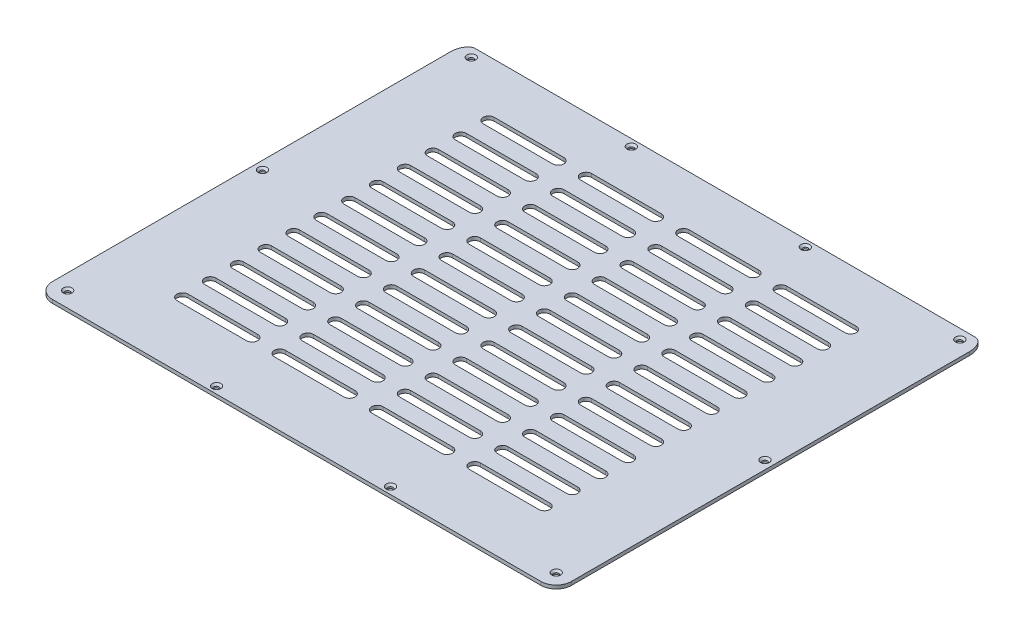
SolidWorks part; units mm, degrees
ref_plane "前基準面" through (0, 0, 0) normal (0, 0, 1) x (1, 0, 0)
ref_plane "上基準面" through (0, 0, 0) normal (0, 1, 0) x (1, 0, 0)
ref_plane "右基準面" through (0, 0, 0) normal (1, 0, 0) x (0, 0, -1)
sketch "草圖1" plane through (0, 0, 0) normal (0, 1, 0) x (1, 0, 0)
  line L1 (-186.5, -154) -> (186.5, -154)
  line L2 (-186.5, -154) -> (-186.5, 154)
  line L3 (-186.5, 154) -> (186.5, 154)
  line L4 (186.5, -154) -> (186.5, 154)
  line L5 (-186.5, -154) -> (186.5, 154) construction
  line L6 (-186.5, 154) -> (186.5, -154) construction
  point P0 (0, 0)
  dimension "D1" = 373
  dimension "D2" = 308
extrude "填料-伸長1" add sketch "草圖1" along normal blind 2.5
fillet "圓角1" radius 11 2 edges at (-186.5, 1.25, 154) (186.5, 1.25, 154)
fillet "圓角2" radius 7 1 edges at (-186.5, 1.25, -154) second distance 11 first distance on face at (0, 1.25, -154)
fillet "圓角3" radius 11 1 edges at (186.5, 1.25, -154) second distance 7 first distance on face at (186.5, 1.25, -5.5)
hole_wizard "M3 錐坑平頭螺釘的錐孔1" positions "草圖2" profile "草圖3" countersink size "M3" standard "ISO" end condition through all
sketch "草圖2" plane through (0, 2.5, 0) normal (0, 1, 0) x (1, 0, 0)
  line L0 (-175.5, -154) -> (175.5, -154) construction
  line L1 (-186.5, 143) -> (-186.5, -143) construction
  line L3 (179.5, 154) -> (-179.5, 154) construction
  line L4 (186.5, -143) -> (186.5, 143) construction
  point P0 (-175.5, 147)
  point P2 (-62.5, 149)
  point P4 (62.5, 149)
  point P6 (175.5, 147)
  point P8 (180.5, 2)
  point P10 (175.5, -143)
  point P12 (62.5, -149)
  point P14 (-62.5, -149)
  point P16 (-175.5, -143)
  point P18 (-180.5, 2)
  dimension "D1" = 11
  dimension "D2" = 11
  dimension "D3" = 113
  dimension "D4" = 125
  dimension "D5" = 113
  dimension "D6" = 11
  dimension "D7" = 5
  dimension "D8" = 5
  dimension "D9" = 5
  dimension "D10" = 5
  dimension "D11" = 7
  dimension "D12" = 7
  dimension "D13" = 11
  dimension "D14" = 6
  dimension "D15" = 6
  dimension "D16" = 11
  dimension "D17" = 145
  dimension "D18" = 145
  dimension "D19" = 113
  dimension "D20" = 125
sketch "草圖3" plane through (-175.5, 2.5, -147) normal (1, 0, 0) x (0, 0, 1)
  line L0 (0, 0) -> (0, 2.555)
  line L1 (0, 2.555) -> (1.8, 2.555)
  line L2 (1.8, 2.555) -> (1.8, 1.35)
  line L3 (1.8, 1.35) -> (3.15, 0)
  line L5 (3.15, 0) -> (0, 0)
  line L6 (-1.8, 1.35) -> (-3.15, 0) construction
  line L11 (0, -6.35) -> (0, 107.95) construction
  dimension "貫穿孔直徑" = 3.6
  dimension "貫穿孔深度" = 2.555
  dimension "近端錐孔直徑" = 6.3
  dimension "近端錐孔角度" = 90
sketch "草圖4" plane through (0, 2.5, 0) normal (0, 1, 0) x (1, 0, 0)
  line L0 (-130, 114) -> (-80, 114) construction
  line L1 (-130, 118) -> (-80, 118)
  line L2 (-130, 110) -> (-80, 110)
  line L3 (-186.5, 143) -> (-186.5, -143) construction
  line L4 (179.5, 154) -> (-179.5, 154) construction
  line L5 (-60, 114) -> (-10, 114) construction
  line L6 (-60, 118) -> (-10, 118)
  line L7 (-60, 110) -> (-10, 110)
  line L8 (10, 114) -> (60, 114) construction
  line L9 (10, 118) -> (60, 118)
  line L10 (10, 110) -> (60, 110)
  line L11 (80, 114) -> (130, 114) construction
  line L12 (80, 118) -> (130, 118)
  line L13 (80, 110) -> (130, 110)
  line L14 (-60, 94) -> (-10, 94) construction
  line L15 (-60, 98) -> (-10, 98)
  line L16 (-60, 90) -> (-10, 90)
  line L17 (10, 94) -> (60, 94) construction
  line L18 (10, 98) -> (60, 98)
  line L19 (10, 90) -> (60, 90)
  line L20 (80, 94) -> (130, 94) construction
  line L21 (80, 98) -> (130, 98)
  line L22 (80, 90) -> (130, 90)
  line L23 (-60, 74) -> (-10, 74) construction
  line L24 (-60, 78) -> (-10, 78)
  line L25 (-60, 70) -> (-10, 70)
  line L26 (10, 74) -> (60, 74) construction
  line L27 (10, 78) -> (60, 78)
  line L28 (10, 70) -> (60, 70)
  line L29 (80, 74) -> (130, 74) construction
  line L30 (80, 78) -> (130, 78)
  line L31 (80, 70) -> (130, 70)
  line L32 (-60, 54) -> (-10, 54) construction
  line L33 (-60, 58) -> (-10, 58)
  line L34 (-60, 50) -> (-10, 50)
  line L35 (10, 54) -> (60, 54) construction
  line L36 (10, 58) -> (60, 58)
  line L37 (10, 50) -> (60, 50)
  line L38 (80, 54) -> (130, 54) construction
  line L39 (80, 58) -> (130, 58)
  line L40 (80, 50) -> (130, 50)
  line L41 (-60, 34) -> (-10, 34) construction
  line L42 (-60, 38) -> (-10, 38)
  line L43 (-60, 30) -> (-10, 30)
  line L44 (10, 34) -> (60, 34) construction
  line L45 (10, 38) -> (60, 38)
  line L46 (10, 30) -> (60, 30)
  line L47 (80, 34) -> (130, 34) construction
  line L48 (80, 38) -> (130, 38)
  line L49 (80, 30) -> (130, 30)
  line L50 (-60, 14) -> (-10, 14) construction
  line L51 (-60, 18) -> (-10, 18)
  line L52 (-60, 10) -> (-10, 10)
  line L53 (10, 14) -> (60, 14) construction
  line L54 (10, 18) -> (60, 18)
  line L55 (10, 10) -> (60, 10)
  line L56 (80, 14) -> (130, 14) construction
  line L57 (80, 18) -> (130, 18)
  line L58 (80, 10) -> (130, 10)
  line L59 (-60, -6) -> (-10, -6) construction
  line L60 (-60, -2) -> (-10, -2)
  line L61 (-60, -10) -> (-10, -10)
  line L62 (10, -6) -> (60, -6) construction
  line L63 (10, -2) -> (60, -2)
  line L64 (10, -10) -> (60, -10)
  line L65 (80, -6) -> (130, -6) construction
  line L66 (80, -2) -> (130, -2)
  line L67 (80, -10) -> (130, -10)
  line L68 (-60, -26) -> (-10, -26) construction
  line L69 (-60, -22) -> (-10, -22)
  line L70 (-60, -30) -> (-10, -30)
  line L71 (10, -26) -> (60, -26) construction
  line L72 (10, -22) -> (60, -22)
  line L73 (10, -30) -> (60, -30)
  line L74 (80, -26) -> (130, -26) construction
  line L75 (80, -22) -> (130, -22)
  line L76 (80, -30) -> (130, -30)
  line L77 (-60, -46) -> (-10, -46) construction
  line L78 (-60, -42) -> (-10, -42)
  line L79 (-60, -50) -> (-10, -50)
  line L80 (10, -46) -> (60, -46) construction
  line L81 (10, -42) -> (60, -42)
  line L82 (10, -50) -> (60, -50)
  line L83 (80, -46) -> (130, -46) construction
  line L84 (80, -42) -> (130, -42)
  line L85 (80, -50) -> (130, -50)
  line L86 (-60, -66) -> (-10, -66) construction
  line L87 (-60, -62) -> (-10, -62)
  line L88 (-60, -70) -> (-10, -70)
  line L89 (10, -66) -> (60, -66) construction
  line L90 (10, -62) -> (60, -62)
  line L91 (10, -70) -> (60, -70)
  line L92 (80, -66) -> (130, -66) construction
  line L93 (80, -62) -> (130, -62)
  line L94 (80, -70) -> (130, -70)
  line L95 (-60, -86) -> (-10, -86) construction
  line L96 (-60, -82) -> (-10, -82)
  line L97 (-60, -90) -> (-10, -90)
  line L98 (10, -86) -> (60, -86) construction
  line L99 (10, -82) -> (60, -82)
  line L100 (10, -90) -> (60, -90)
  line L101 (80, -86) -> (130, -86) construction
  line L102 (80, -82) -> (130, -82)
  line L103 (80, -90) -> (130, -90)
  line L104 (-60, -106) -> (-10, -106) construction
  line L105 (-60, -102) -> (-10, -102)
  line L106 (-60, -110) -> (-10, -110)
  line L107 (10, -106) -> (60, -106) construction
  line L108 (10, -102) -> (60, -102)
  line L109 (10, -110) -> (60, -110)
  line L110 (80, -106) -> (130, -106) construction
  line L111 (80, -102) -> (130, -102)
  line L112 (80, -110) -> (130, -110)
  line L113 (-130, 94) -> (-80, 94) construction
  line L114 (-130, 98) -> (-80, 98)
  line L115 (-130, 90) -> (-80, 90)
  line L116 (-130, 74) -> (-80, 74) construction
  line L117 (-130, 78) -> (-80, 78)
  line L118 (-130, 70) -> (-80, 70)
  line L119 (-130, 54) -> (-80, 54) construction
  line L120 (-130, 58) -> (-80, 58)
  line L121 (-130, 50) -> (-80, 50)
  line L122 (-130, 34) -> (-80, 34) construction
  line L123 (-130, 38) -> (-80, 38)
  line L124 (-130, 30) -> (-80, 30)
  line L125 (-130, 14) -> (-80, 14) construction
  line L126 (-130, 18) -> (-80, 18)
  line L127 (-130, 10) -> (-80, 10)
  line L128 (-130, -6) -> (-80, -6) construction
  line L129 (-130, -2) -> (-80, -2)
  line L130 (-130, -10) -> (-80, -10)
  line L131 (-130, -26) -> (-80, -26) construction
  line L132 (-130, -22) -> (-80, -22)
  line L133 (-130, -30) -> (-80, -30)
  line L134 (-130, -46) -> (-80, -46) construction
  line L135 (-130, -42) -> (-80, -42)
  line L136 (-130, -50) -> (-80, -50)
  line L137 (-130, -66) -> (-80, -66) construction
  line L138 (-130, -62) -> (-80, -62)
  line L139 (-130, -70) -> (-80, -70)
  line L140 (-130, -86) -> (-80, -86) construction
  line L141 (-130, -82) -> (-80, -82)
  line L142 (-130, -90) -> (-80, -90)
  line L143 (-130, -106) -> (-80, -106) construction
  line L144 (-130, -102) -> (-80, -102)
  line L145 (-130, -110) -> (-80, -110)
  arc A0 (-130, 118) -> (-130, 110) centre (-130, 114) ccw
  arc A1 (-80, 110) -> (-80, 118) centre (-80, 114) ccw
  arc A2 (-60, 118) -> (-60, 110) centre (-60, 114) ccw
  arc A3 (-10, 110) -> (-10, 118) centre (-10, 114) ccw
  arc A4 (10, 118) -> (10, 110) centre (10, 114) ccw
  arc A5 (60, 110) -> (60, 118) centre (60, 114) ccw
  arc A6 (80, 118) -> (80, 110) centre (80, 114) ccw
  arc A7 (130, 110) -> (130, 118) centre (130, 114) ccw
  arc A8 (-60, 98) -> (-60, 90) centre (-60, 94) ccw
  arc A9 (-10, 90) -> (-10, 98) centre (-10, 94) ccw
  arc A10 (10, 98) -> (10, 90) centre (10, 94) ccw
  arc A11 (60, 90) -> (60, 98) centre (60, 94) ccw
  arc A12 (80, 98) -> (80, 90) centre (80, 94) ccw
  arc A13 (130, 90) -> (130, 98) centre (130, 94) ccw
  arc A14 (-60, 78) -> (-60, 70) centre (-60, 74) ccw
  arc A15 (-10, 70) -> (-10, 78) centre (-10, 74) ccw
  arc A16 (10, 78) -> (10, 70) centre (10, 74) ccw
  arc A17 (60, 70) -> (60, 78) centre (60, 74) ccw
  arc A18 (80, 78) -> (80, 70) centre (80, 74) ccw
  arc A19 (130, 70) -> (130, 78) centre (130, 74) ccw
  arc A20 (-60, 58) -> (-60, 50) centre (-60, 54) ccw
  arc A21 (-10, 50) -> (-10, 58) centre (-10, 54) ccw
  arc A22 (10, 58) -> (10, 50) centre (10, 54) ccw
  arc A23 (60, 50) -> (60, 58) centre (60, 54) ccw
  arc A24 (80, 58) -> (80, 50) centre (80, 54) ccw
  arc A25 (130, 50) -> (130, 58) centre (130, 54) ccw
  arc A26 (-60, 38) -> (-60, 30) centre (-60, 34) ccw
  arc A27 (-10, 30) -> (-10, 38) centre (-10, 34) ccw
  arc A28 (10, 38) -> (10, 30) centre (10, 34) ccw
  arc A29 (60, 30) -> (60, 38) centre (60, 34) ccw
  arc A30 (80, 38) -> (80, 30) centre (80, 34) ccw
  arc A31 (130, 30) -> (130, 38) centre (130, 34) ccw
  arc A32 (-60, 18) -> (-60, 10) centre (-60, 14) ccw
  arc A33 (-10, 10) -> (-10, 18) centre (-10, 14) ccw
  arc A34 (10, 18) -> (10, 10) centre (10, 14) ccw
  arc A35 (60, 10) -> (60, 18) centre (60, 14) ccw
  arc A36 (80, 18) -> (80, 10) centre (80, 14) ccw
  arc A37 (130, 10) -> (130, 18) centre (130, 14) ccw
  arc A38 (-60, -2) -> (-60, -10) centre (-60, -6) ccw
  arc A39 (-10, -10) -> (-10, -2) centre (-10, -6) ccw
  arc A40 (10, -2) -> (10, -10) centre (10, -6) ccw
  arc A41 (60, -10) -> (60, -2) centre (60, -6) ccw
  arc A42 (80, -2) -> (80, -10) centre (80, -6) ccw
  arc A43 (130, -10) -> (130, -2) centre (130, -6) ccw
  arc A44 (-60, -22) -> (-60, -30) centre (-60, -26) ccw
  arc A45 (-10, -30) -> (-10, -22) centre (-10, -26) ccw
  arc A46 (10, -22) -> (10, -30) centre (10, -26) ccw
  arc A47 (60, -30) -> (60, -22) centre (60, -26) ccw
  arc A48 (80, -22) -> (80, -30) centre (80, -26) ccw
  arc A49 (130, -30) -> (130, -22) centre (130, -26) ccw
  arc A50 (-60, -42) -> (-60, -50) centre (-60, -46) ccw
  arc A51 (-10, -50) -> (-10, -42) centre (-10, -46) ccw
  arc A52 (10, -42) -> (10, -50) centre (10, -46) ccw
  arc A53 (60, -50) -> (60, -42) centre (60, -46) ccw
  arc A54 (80, -42) -> (80, -50) centre (80, -46) ccw
  arc A55 (130, -50) -> (130, -42) centre (130, -46) ccw
  arc A56 (-60, -62) -> (-60, -70) centre (-60, -66) ccw
  arc A57 (-10, -70) -> (-10, -62) centre (-10, -66) ccw
  arc A58 (10, -62) -> (10, -70) centre (10, -66) ccw
  arc A59 (60, -70) -> (60, -62) centre (60, -66) ccw
  arc A60 (80, -62) -> (80, -70) centre (80, -66) ccw
  arc A61 (130, -70) -> (130, -62) centre (130, -66) ccw
  arc A62 (-60, -82) -> (-60, -90) centre (-60, -86) ccw
  arc A63 (-10, -90) -> (-10, -82) centre (-10, -86) ccw
  arc A64 (10, -82) -> (10, -90) centre (10, -86) ccw
  arc A65 (60, -90) -> (60, -82) centre (60, -86) ccw
  arc A66 (80, -82) -> (80, -90) centre (80, -86) ccw
  arc A67 (130, -90) -> (130, -82) centre (130, -86) ccw
  arc A68 (-60, -102) -> (-60, -110) centre (-60, -106) ccw
  arc A69 (-10, -110) -> (-10, -102) centre (-10, -106) ccw
  arc A70 (10, -102) -> (10, -110) centre (10, -106) ccw
  arc A71 (60, -110) -> (60, -102) centre (60, -106) ccw
  arc A72 (80, -102) -> (80, -110) centre (80, -106) ccw
  arc A73 (130, -110) -> (130, -102) centre (130, -106) ccw
  arc A74 (-130, 98) -> (-130, 90) centre (-130, 94) ccw
  arc A75 (-80, 90) -> (-80, 98) centre (-80, 94) ccw
  arc A76 (-130, 78) -> (-130, 70) centre (-130, 74) ccw
  arc A77 (-80, 70) -> (-80, 78) centre (-80, 74) ccw
  arc A78 (-130, 58) -> (-130, 50) centre (-130, 54) ccw
  arc A79 (-80, 50) -> (-80, 58) centre (-80, 54) ccw
  arc A80 (-130, 38) -> (-130, 30) centre (-130, 34) ccw
  arc A81 (-80, 30) -> (-80, 38) centre (-80, 34) ccw
  arc A82 (-130, 18) -> (-130, 10) centre (-130, 14) ccw
  arc A83 (-80, 10) -> (-80, 18) centre (-80, 14) ccw
  arc A84 (-130, -2) -> (-130, -10) centre (-130, -6) ccw
  arc A85 (-80, -10) -> (-80, -2) centre (-80, -6) ccw
  arc A86 (-130, -22) -> (-130, -30) centre (-130, -26) ccw
  arc A87 (-80, -30) -> (-80, -22) centre (-80, -26) ccw
  arc A88 (-130, -42) -> (-130, -50) centre (-130, -46) ccw
  arc A89 (-80, -50) -> (-80, -42) centre (-80, -46) ccw
  arc A90 (-130, -62) -> (-130, -70) centre (-130, -66) ccw
  arc A91 (-80, -70) -> (-80, -62) centre (-80, -66) ccw
  arc A92 (-130, -82) -> (-130, -90) centre (-130, -86) ccw
  arc A93 (-80, -90) -> (-80, -82) centre (-80, -86) ccw
  arc A94 (-130, -102) -> (-130, -110) centre (-130, -106) ccw
  arc A95 (-80, -110) -> (-80, -102) centre (-80, -106) ccw
  point P2 (-105, 114)
  point P16 (-35, 114)
  point P23 (35, 114)
  point P30 (105, 114)
  point P37 (-35, 94)
  point P44 (35, 94)
  point P51 (105, 94)
  point P58 (-35, 74)
  point P65 (35, 74)
  point P72 (105, 74)
  point P79 (-35, 54)
  point P86 (35, 54)
  point P93 (105, 54)
  point P100 (-35, 34)
  point P107 (35, 34)
  point P114 (105, 34)
  point P121 (-35, 14)
  point P128 (35, 14)
  point P135 (105, 14)
  point P142 (-35, -6)
  point P149 (35, -6)
  point P156 (105, -6)
  point P163 (-35, -26)
  point P170 (35, -26)
  point P177 (105, -26)
  point P184 (-35, -46)
  point P191 (35, -46)
  point P198 (105, -46)
  point P205 (-35, -66)
  point P212 (35, -66)
  point P219 (105, -66)
  point P226 (-35, -86)
  point P233 (35, -86)
  point P240 (105, -86)
  point P247 (-35, -106)
  point P254 (35, -106)
  point P261 (105, -106)
  point P268 (-105, 94)
  point P275 (-105, 74)
  point P282 (-105, 54)
  point P289 (-105, 34)
  point P296 (-105, 14)
  point P303 (-105, -6)
  point P310 (-105, -26)
  point P317 (-105, -46)
  point P324 (-105, -66)
  point P331 (-105, -86)
  point P338 (-105, -106)
  dimension "D2" = 4
  dimension "D1" = 50
  dimension "D3" = 81.5
  dimension "D4" = 40
  dimension "D5" = 4
  dimension "D6" = 12
extrude "除料-伸長1" cut sketch "草圖4" against normal blind 2.5
